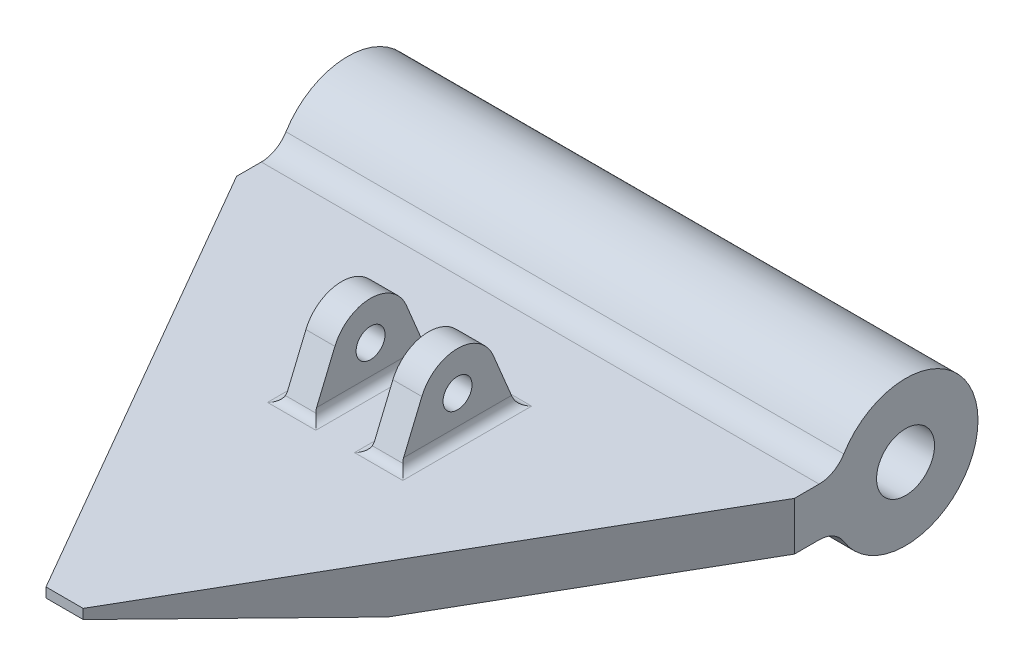
SolidWorks part; units mm, degrees
material "Custom Plastic"
ref_plane "Front Plane" through (0, 0, 0) normal (0, 0, 1) x (1, 0, 0)
ref_plane "Top Plane" through (0, 0, 0) normal (0, 1, 0) x (1, 0, 0)
ref_plane "Right Plane" through (0, 0, 0) normal (1, 0, 0) x (0, 0, -1)
sketch "Sketch1" plane through (0, 0, 0) normal (0, 1, 0) x (1, 0, 0)
  line L0 (-28.8675, 50) -> (-28.8675, 70)
  line L1 (28.8675, 50) -> (-28.8675, 50) construction
  line L2 (-28.8675, 50) -> (-57.735, 0) construction
  line L3 (-57.735, 0) -> (-28.8675, -50) construction
  line L4 (-28.8675, -50) -> (28.8675, -50) construction
  line L5 (28.8675, -50) -> (57.735, 0) construction
  line L6 (57.735, 0) -> (28.8675, 50) construction
  line L7 (-28.8675, 70) -> (28.8675, 70)
  line L8 (28.8675, 70) -> (28.8675, 50)
  line L9 (28.8675, 50) -> (0, 0)
  line L10 (0, 0) -> (-28.8675, 50)
  circle A0 centre (0, 0) radius 50 construction
  dimension "D1" = 100
  dimension "D2" = 20
extrude "Boss-Extrude1" add sketch "Sketch1" along normal blind 5
sketch "Sketch2" plane through (28.8675, 0, 0) normal (1, 0, 0) x (0, 0, -1)
  line L0 (50, 5) -> (50, 0) construction
  line L1 (70, 5) -> (70, 0) construction
  circle A0 centre (62.5, 2.5) radius 7.5
  circle A1 centre (62.5, 2.5) radius 3
  point P6 (50, 2.5)
  line M3 (50, 0) -> (70, 0)
  line M4 (70, 0) -> (70, 5)
  line M5 (70, 5) -> (50, 5)
  dimension "D1" = 15
  dimension "D2" = 6
extrude "Boss-Extrude2" add sketch "Sketch2" against normal up to surface (57.735 mm away) up to face at (-28.8675, 2.5, -60)
extrude "Cut-Extrude1" cut sketch "Sketch2<2>" against normal up to surface (57.735 mm away) contours A1 M5 M3 | A1 M5 | A1 M3 | A0 M4 M5 | A0 M3 M4 region at (28.8675, 0.6214, -69.872) region at (28.8675, 4.3786, -69.872) region at (28.8675, 5.2015, -62.5) region at (28.8675, 2.5, -62.5) region at (28.8675, -0.2015, -62.5) up to face at (-28.8675, 2.5, -61.25)
sketch "Sketch2<2>" plane through (28.8675, 0, 0) normal (1, 0, 0) x (0, 0, -1) same geometry as "Sketch2"
sketch "Sketch3" plane through (0, 5, 0) normal (0, 1, 0) x (1, 0, 0)
  line L0 (-2.5, 4.3301) -> (2.5, 4.3301)
  line L1 (-28.8675, 50) -> (0, 0) construction
  line L2 (0, 0) -> (28.8675, 50) construction
  line L8 (28.8675, 50) -> (28.8675, 55.4289)
  line L9 (28.8675, 55.4289) -> (-28.8675, 55.4289)
  line L10 (-28.8675, 55.4289) -> (-28.8675, 50)
  line L11 (-28.8675, 50) -> (0, 0)
  line L12 (0, 0) -> (28.8675, 50)
  line L16 (-2.5, 4.3301) -> (0, 0)
  line L17 (0, 0) -> (2.5, 4.3301)
  dimension "D1" = 5
  dimension "D2" = 0
extrude "Cut-Extrude2" cut sketch "Sketch3" against normal up to surface (5 mm away) up to face at (0, 0, -42.1716)
fillet "Fillet1" radius 3 2 edges at (0, 0, -55.4289) (0, 5, -55.4289)
sketch "Sketch4" plane through (0, 0, 0) normal (0.866, 0, 0.5) x (0.5, 0, -0.866)
  line L0 (57.735, 0) -> (60.8144, 0) construction
  line L1 (60.8144, 5) -> (57.735, 5) construction
  line L2 (57.735, 5) -> (5, 5) construction
  line L3 (5, 0) -> (57.735, 0) construction
  line L4 (5, 5) -> (2.5, 5) construction
  line L5 (2.5, 5) -> (2.5, 0) construction
  line L6 (2.5, 0) -> (5, 0) construction
  line L7 (57.735, 0) -> (60.8144, 0)
  line L8 (60.8144, 5) -> (57.735, 5)
  line L9 (57.735, 5) -> (5, 5)
  line L10 (5, 0) -> (57.735, 0)
  line L11 (5, 5) -> (2.5, 5)
  line L12 (2.5, 5) -> (2.5, 0)
  line L13 (2.5, 0) -> (5, 0)
  ellipse E0 centre (60.8144, -3) end of major axis (60.8144, -6) minor radius 2.5981 (63.0275, -1.4286) -> (60.8144, 0) ccw construction
  ellipse E1 centre (68.5603, 2.5) end of major axis (68.5603, -5) minor radius 6.4952 (63.0275, -1.4286) -> (63.0275, 6.4286) ccw construction
  ellipse E2 centre (60.8144, 8) end of major axis (60.8144, 5) minor radius 2.5981 (60.8144, 5) -> (63.0275, 6.4286) ccw construction
  ellipse E3 centre (60.8144, -3) end of major axis (60.8144, -6) minor radius 2.5981 (63.0275, -1.4286) -> (60.8144, 0) ccw
  ellipse E4 centre (68.5603, 2.5) end of major axis (68.5603, -5) minor radius 6.4952 (63.0275, -1.4286) -> (63.0275, 6.4286) ccw
  ellipse E5 centre (60.8144, 8) end of major axis (60.8144, 11) minor radius 2.5981 (60.8144, 5) -> (63.0275, 6.4286) ccw
extrude "Cut-Extrude3" cut sketch "Sketch4" against normal blind 0.5
mirror "Mirror1" about plane through (0, 0, 0) normal (1, 0, 0) of "Cut-Extrude3"
chamfer "Chamfer1" distance 4 distance2 20 1 edges at (0, 0, -4.3301) first distance on face at (0, 2.5, -4.3301)
sketch "Sketch5" plane through (0, 0, 0) normal (1, 0, 0) x (0, 0, -1)
  line L0 (35.3077, 10.5385) -> (33, 5)
  line L1 (51, 5) -> (4.3301, 5) construction
  line L2 (33, 5) -> (45, 5)
  line L3 (45, 5) -> (42.6923, 10.5385)
  line L4 (51, 0) -> (51, 5) construction
  circle A0 centre (39, 9) radius 1.5
  arc A1 (42.6923, 10.5385) -> (35.3077, 10.5385) centre (39, 9) ccw
  point P2 (39, 13)
  point P7 (37.7012, 9)
  point P10 (38.7653, 9)
  dimension "D1" = 3
  dimension "D2" = 4
  dimension "D3" = 8
  dimension "D4" = 12
  dimension "D5" = 6
extrude "Boss-Extrude3" add sketch "Sketch5" along normal blind 3 from offset 3
mirror "Mirror2" about plane through (0, 0, 0) normal (1, 0, 0) of "Boss-Extrude3"
fillet "Fillet2" radius 1 8 edges at (4.5, 5, -45) (-4.5, 5, -45) (-3, 5, -39) (3, 5, -39) (4.5, 5, -33) (-4.5, 5, -33) (-6, 5, -39) (6, 5, -39)
